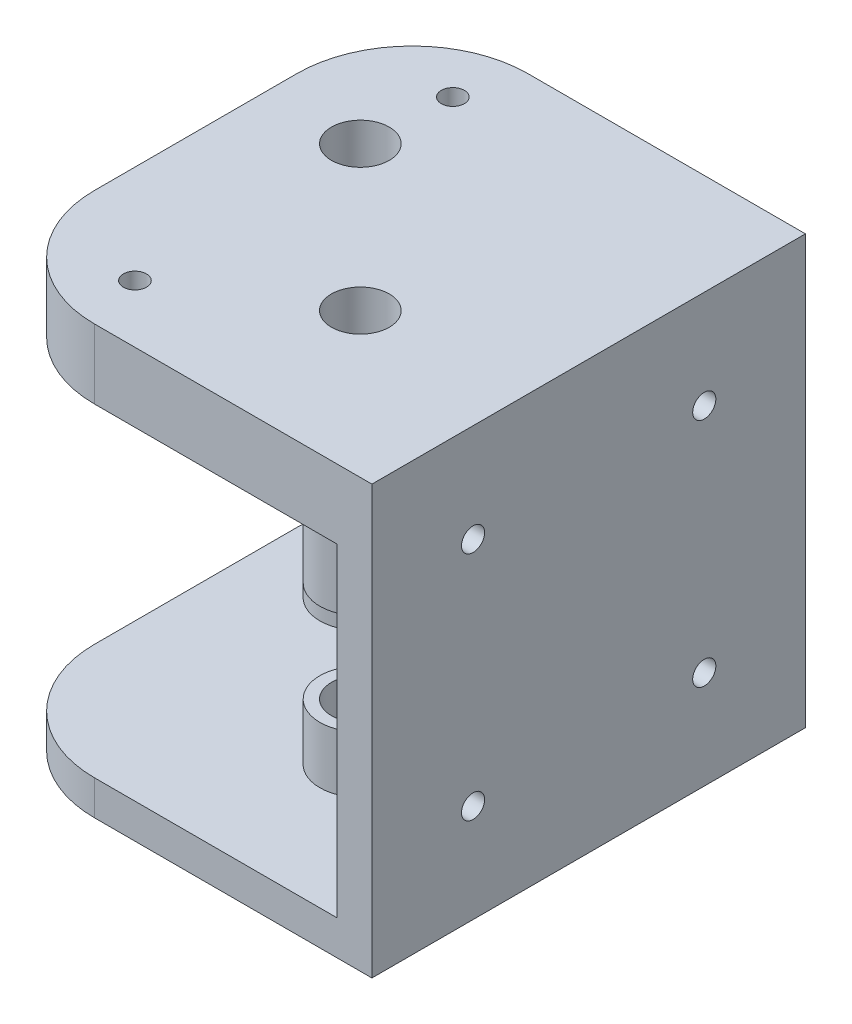
SolidWorks part; units mm, degrees
ref_plane "Front Plane" through (0, 0, 0) normal (0, 0, 1) x (1, 0, 0)
ref_plane "Top Plane" through (0, 0, 0) normal (0, 1, 0) x (1, 0, 0)
ref_plane "Right Plane" through (0, 0, 0) normal (1, 0, 0) x (0, 0, -1)
sketch "TopSketch1" plane through (0, 0, 0) normal (0, 1, 0) x (1, 0, 0)
  line L1 (0, 0) -> (34, 0)
  line L2 (0, 0) -> (0, 37.5)
  line L3 (0, 37.5) -> (34, 37.5)
  line L4 (34, 0) -> (34, 37.5)
  circle A0 centre (8.5, 32.5) radius 1
  circle A1 centre (8.5, 5) radius 1
  circle A2 centre (20.5, 12.5) radius 2.5
  circle A3 centre (8, 25) radius 2.5
  dimension "D7" = 2
  dimension "D8" = 5
  dimension "D2" = 12.5
  dimension "D3" = 12.5
  dimension "D4" = 5
  dimension "D5" = 5
  dimension "D10" = 37.5
  dimension "D9" = 12.5
  dimension "D12" = 13.5
  dimension "D6" = 25.5
  dimension "D11" = 8
  dimension "D13" = 12.5
extrude "Boss-Extrude1" add sketch "TopSketch1" along normal blind 6
sketch "TopLeftRiser" plane through (0, 0, 0) normal (0, -1, 0) x (1, 0, 0)
  line L0 (5.75, -27.681) -> (5.75, -37.5)
  line L1 (34, -37.5) -> (0, -37.5) construction
  line L2 (5.75, -37.5) -> (10.25, -37.5)
  line L3 (10.25, -37.5) -> (10.25, -27.681)
  arc A0 (10.25, -27.681) -> (5.75, -27.681) centre (8, -25) ccw
  circle A1 centre (8, -25) radius 2.5 construction
  circle A2 centre (8, -25) radius 2.5
  point P12 (8, -37.5)
  dimension "D1" = 7
  dimension "D2" = 4.5
extrude "TopLeftRiserBoss-Extrude2" add sketch "TopLeftRiser" along normal blind 4.9
sketch "TopRightRiser" plane through (0, 0, 0) normal (0, -1, 0) x (1, 0, 0)
  line L0 (18.25, -15.181) -> (18.25, -37.5)
  line L1 (34, -37.5) -> (10.25, -37.5) construction
  line L2 (18.25, -37.5) -> (22.75, -37.5)
  line L3 (22.75, -37.5) -> (22.75, -15.181)
  line L4 (5.75, -37.5) -> (10.25, -37.5) construction
  circle A0 centre (20.5, -12.5) radius 2.5
  circle A1 centre (20.5, -12.5) radius 2.5 construction
  arc A2 (22.75, -15.181) -> (18.25, -15.181) centre (20.5, -12.5) ccw
  arc A3 (10.25, -27.681) -> (5.75, -27.681) centre (8, -25) ccw construction
  point P15 (20.5, -37.5)
extrude "topRightRiserBoss-Extrude3" add sketch "TopRightRiser" along normal blind 14.4
sketch "MidWallSketch3" plane through (0, 0, 0) normal (0, -1, 0) x (1, 0, 0)
  line L1 (0, -34.5) -> (10.25, -34.5)
  line L2 (0, -34.5) -> (0, -37.5)
  line L3 (0, -37.5) -> (10.25, -37.5)
  line L4 (10.25, -34.5) -> (10.25, -37.5)
  line L5 (18.25, -34.5) -> (22.75, -34.5)
  line L6 (18.25, -34.5) -> (18.25, -37.5)
  line L7 (18.25, -37.5) -> (22.75, -37.5)
  line L8 (22.75, -34.5) -> (22.75, -37.5)
  line L9 (34, 0) -> (34, -37.5)
  line L10 (34, -37.5) -> (31, -37.5)
  line L11 (31, -37.5) -> (31, 0)
  line L14 (10.25, -37.5) -> (10.25, -27.681) construction
  line L15 (0, -37.5) -> (0, 0) construction
  line L16 (34, -37.5) -> (0, -37.5) construction
  line L17 (31, 0) -> (34, 0)
  line L19 (34, 0) -> (34, -37.5) construction
  line L20 (0, 0) -> (34, 0) construction
  line L21 (22.75, -37.5) -> (22.75, -15.181) construction
  line L22 (18.25, -15.181) -> (18.25, -37.5) construction
  dimension "D1" = 3
extrude "WallBoss-Extrude4" add sketch "MidWallSketch3" along normal blind 28
sketch "BottomSketch4" plane through (0, -28, 0) normal (0, -1, 0) x (1, 0, 0)
  line L0 (0, 0) -> (34, 0) construction
  line L1 (0, 0) -> (34, 0)
  line L2 (0, 0) -> (0, -37.5)
  line L3 (0, -37.5) -> (34, -37.5)
  line L4 (34, 0) -> (34, -37.5)
  line L5 (34, 0) -> (34, -37.5) construction
  line L6 (34, -37.5) -> (0, -37.5) construction
extrude "BottomBoss-Extrude5" add sketch "BottomSketch4" along normal blind 3
sketch "LowerLeftRiser" plane through (0, -28, 0) normal (0, 1, 0) x (1, 0, 0)
  line L0 (5.75, 27.681) -> (5.75, 34.5)
  line L1 (5.75, 34.5) -> (10.25, 34.5)
  line L2 (10.25, 34.5) -> (10.25, 27.681)
  line L3 (5.75, 34.5) -> (10.25, 34.5) construction
  line L4 (5.75, 27.681) -> (5.75, 34.5) construction
  line L5 (10.25, 34.5) -> (10.25, 27.681) construction
  circle A0 centre (8, 25) radius 2.5
  arc A1 (5.75, 27.681) -> (10.25, 27.681) centre (8, 25) ccw
  circle A2 centre (8, 25) radius 2.5 construction
  arc A3 (5.75, 27.681) -> (10.25, 27.681) centre (8, 25) ccw construction
extrude "LowerLeftRiserBoss-Extrude6" add sketch "LowerLeftRiser" along normal blind 14.4
sketch "LowerRightRiser" plane through (0, -28, 0) normal (0, 1, 0) x (1, 0, 0)
  line L0 (18.25, 15.181) -> (18.25, 34.5)
  line L1 (18.25, 34.5) -> (22.75, 34.5)
  line L2 (22.75, 34.5) -> (22.75, 15.181)
  line L3 (18.25, 34.5) -> (22.75, 34.5) construction
  line L4 (18.25, 15.181) -> (18.25, 34.5) construction
  line L5 (22.75, 34.5) -> (22.75, 15.181) construction
  circle A0 centre (20.5, 12.5) radius 2.5
  circle A1 centre (20.5, 12.5) radius 2.5 construction
  arc A2 (18.25, 15.181) -> (22.75, 15.181) centre (20.5, 12.5) ccw
  arc A3 (18.25, 15.181) -> (22.75, 15.181) centre (20.5, 12.5) ccw construction
extrude "LowerRightRiserBoss-Extrude7" add sketch "LowerRightRiser" along normal blind 4.9
fillet "Fillet1" radius 10 3 edges at (0, -29.5, 0) (0, 3, 0) (0, -12.5, -37.5)
sketch "GBMountingHolesSketch7" plane through (34, 0, 0) normal (1, 0, 0) x (0, 0, -1)
  line L0 (37.5, 6) -> (37.5, -31) construction
  line L1 (0, 6) -> (37.5, 6) construction
  line L2 (37.5, -31) -> (0, -31) construction
  line L3 (0, 6) -> (0, -31) construction
  circle A0 centre (8.75, -2.5) radius 1
  circle A1 centre (8.75, -22.5) radius 1
  circle A2 centre (28.75, -22.5) radius 1
  circle A3 centre (28.75, -2.5) radius 1
  dimension "D7" = 2
  dimension "D1" = 20
  dimension "D2" = 8.75
  dimension "D3" = 8.5
  dimension "D4" = 20
  dimension "D5" = 8.5
  dimension "D6" = 8.75
sketch "TopLeftInset" plane through (0, -4.9, 0) normal (0, -1, 0) x (1, 0, 0)
  line L0 (5.75, -27.681) -> (5.75, -34.5)
  line L1 (5.75, -34.5) -> (10.25, -34.5)
  line L2 (10.25, -34.5) -> (10.25, -27.681)
  line L3 (10.25, -34.5) -> (5.75, -34.5) construction
  line L4 (5.75, -34.5) -> (5.75, -27.681) construction
  line L5 (10.25, -27.681) -> (10.25, -34.5) construction
  arc A0 (5.75, -27.681) -> (10.25, -27.681) centre (8, -25) ccw
  arc A1 (10.25, -27.681) -> (5.75, -27.681) centre (8, -25) ccw construction
extrude "TopLeftInsetCut-Extrude1" cut sketch "TopLeftInset" against normal blind 1
sketch "TopRightInset" plane through (0, -14.4, 0) normal (0, -1, 0) x (1, 0, 0)
  line L0 (18.25, -15.181) -> (18.25, -34.5)
  line L1 (18.25, -34.5) -> (22.75, -34.5)
  line L2 (22.75, -34.5) -> (22.75, -15.181)
  line L3 (22.75, -34.5) -> (18.25, -34.5) construction
  line L4 (18.25, -34.5) -> (18.25, -15.181) construction
  line L5 (22.75, -15.181) -> (22.75, -34.5) construction
  arc A0 (18.25, -15.181) -> (22.75, -15.181) centre (20.5, -12.5) ccw
  arc A1 (22.75, -15.181) -> (18.25, -15.181) centre (20.5, -12.5) ccw construction
extrude "TopRightInsetCut-Extrude2" cut sketch "TopRightInset" against normal blind 1
sketch "LowerLeftInset" plane through (0, -13.6, 0) normal (0, 1, 0) x (1, 0, 0)
  line L0 (5.75, 27.681) -> (5.75, 34.5)
  line L1 (5.75, 34.5) -> (10.25, 34.5)
  line L2 (10.25, 34.5) -> (10.25, 27.681)
  line L3 (5.75, 34.5) -> (10.25, 34.5) construction
  line L4 (5.75, 27.681) -> (5.75, 34.5) construction
  line L5 (10.25, 34.5) -> (10.25, 27.681) construction
  arc A0 (10.25, 27.681) -> (5.75, 27.681) centre (8, 25) ccw
  arc A1 (5.75, 27.681) -> (10.25, 27.681) centre (8, 25) ccw construction
extrude "LowerLeftInsetCut-Extrude3" cut sketch "LowerLeftInset" against normal blind 1
sketch "LowerRightInset" plane through (0, -23.1, 0) normal (0, 1, 0) x (1, 0, 0)
  line L0 (18.25, 15.181) -> (18.25, 34.5)
  line L1 (18.25, 34.5) -> (22.75, 34.5)
  line L2 (22.75, 34.5) -> (22.75, 15.181)
  line L3 (18.25, 34.5) -> (22.75, 34.5) construction
  line L4 (18.25, 15.181) -> (18.25, 34.5) construction
  line L5 (22.75, 34.5) -> (22.75, 15.181) construction
  arc A2 (22.75, 15.181) -> (18.25, 15.181) centre (20.5, 12.5) ccw
  arc A3 (18.25, 15.181) -> (22.75, 15.181) centre (20.5, 12.5) ccw construction
extrude "LowerRightInsetCut-Extrude4" cut sketch "LowerRightInset" against normal blind 1
extrude "GBMountingHolesCut-Extrude5" cut sketch "GBMountingHolesSketch7" against normal blind 3
sketch "PushPinHoleSketch1" plane through (0, -31, 0) normal (0, -1, 0) x (1, 0, 0)
  circle A0 centre (20.5, -12.5) radius 1
  circle A1 centre (8, -25) radius 1
  circle A2 centre (8, -25) radius 2.5 construction
  circle A3 centre (20.5, -12.5) radius 2.5 construction
  dimension "D1" = 2
extrude "Cut-Extrude1" cut sketch "PushPinHoleSketch1" against normal through all
equation "\"GABDepth\"= \"GABDistanceFromBackToFirstPulley\" + \"GABPulleyDDistanceBetween\" + \"GABDistanceFromPulleyToFront\""
equation "\"GABWidth\"= \"StandardWallThickness\" + \"GABDistanceFromLSideToPulley\" + \"GABPulleyWDistanceBetween\" + \"GABDistanceFromPulleyToRSide\""
equation "\"GABLowerHeight\"= 3mm"
equation "\"GABUpperHeight\"= 6mm"
equation "\"GABMidWallHeight\"= 28mm'Must equal 28 or changes alignment"
equation "\"StandardWallThickness\"= 3mm"
equation "\"GABMidShortRiserHeight\"= \"GABMidWallHeight\" / 2 - \"20TGT2PulleyWidth\"'Equals 5.3"
equation "\"LinearGBMountHolesXDistance\"= 20mm'Spec"
equation "\"GABHeight\"= \"GABLowerHeight\" + \"GABMidWallHeight\" + \"GABUpperHeight\""
equation "\"GBMountingHoleDiameter\"= 2mm"
equation "\"GABMidLongRiserHeight\"= \"GABMidWallHeight\" - \"GABMidShortRiserHeight\" - \"20TGT2PulleyWidth\"'Equals 14"
equation "\"GABLRClampHoleOffsetFromSide\"= 5mm"
equation "\"GABDistanceFromBackToFirstPulley\"= 13.5mm"
equation "\"GABPulleyDDistanceBetween\"= 12.5mm'From the100"
equation "\"GABPulleyWDistanceBetween\"= 14.5mm'From the100"
equation "\"GABDistanceFromPulleyToFront\"= 8mm"
equation "\"GABDistanceFromLSideToPulley\"= 9.5mm + \"StandardWallThickness\""
equation "\"GABDistanceFromPulleyToRSide\"= 7.5mm"
equation "\"GABDistanceToFrontClampHoles\"= 8.5mm"
equation "\"SteelShaft5mmHoleDiameter\"= 5mm"
equation "\"20TGT2PulleyWidth\"= 8.7mm'The STL of the Pulley in the diagram is a bit larger"
equation "\"7mmx1mmSpacerDiameter\"= 7mm"
equation "\"7mmx1mmSpacerHeight\"= 1mm"
equation "\"GABRiserBossOffset\"= 0.8mm'Aligns Pulleys"
equation "\"D2@TopSketch1\" = \"GABPulleyDDistanceBetween\""
equation "\"D3@TopSketch1\" = \"GABPulleyDDistanceBetween\""
equation "\"D4@TopSketch1\" = \"GABLRClampHoleOffsetFromSide\""
equation "\"D5@TopSketch1\" = \"GABLRClampHoleOffsetFromSide\""
equation "\"D8@TopSketch1\" = \"SteelShaft5mmHoleDiameter\""
equation "\"D10@TopSketch1\" = \"GABWidth\""
equation "\"D9@TopSketch1\" = \"GABDistanceFromLSideToPulley\""
equation "\"D12@TopSketch1\"=\"GABDistanceFromBackToFirstPulley\""
equation "\"D1@Boss-Extrude1\"=\"GABUpperHeight\""
equation "\"D1@TopLeftRiser\" = \"7mmx1mmSpacerDiameter\""
equation "\"D1@TopLeftRiserBoss-Extrude2\"=\"GABMidShortRiserHeight\" - \"GABRiserBossOffset\" / 2"
equation "\"D1@topRightRiserBoss-Extrude3\"=\"GABMidLongRiserHeight\" + \"GABRiserBossOffset\"/2"
equation "\"D1@WallBoss-Extrude4\" = \"GABMidWallHeight\""
equation "\"D1@BottomBoss-Extrude5\" = \"GABLowerHeight\""
equation "\"D1@LowerLeftRiserBoss-Extrude6\"=\"GABMidLongRiserHeight\" + \"GABRiserBossOffset\"/2"
equation "\"D1@LowerRightRiserBoss-Extrude7\"=\"GABMidShortRiserHeight\"-\"GABRiserBossOffset\"/2"
equation "\"D1@GBMountingHolesSketch7\" = \"LinearGBMountHolesXDistance\""
equation "\"D2@GBMountingHolesSketch7\" =  ( \"GABWidth\" - \"LinearGBMountHolesXDistance\" )  / 2"
equation "\"D3@GBMountingHolesSketch7\" =  ( \"GABHeight\" - \"LinearGBMountHolesXDistance\" )  / 2"
equation "\"D4@GBMountingHolesSketch7\"=\"LinearGBMountHolesYDistance\""
equation "\"D7@GBMountingHolesSketch7\"=\"GBMountingHoleDiameter\""
equation "\"D1@TopLeftInsetCut-Extrude1\" = \"7mmx1mmSpacerHeight\""
equation "\"D1@TopRightInsetCut-Extrude2\" = \"7mmx1mmSpacerHeight\""
equation "\"D1@LowerLeftInsetCut-Extrude3\" = \"7mmx1mmSpacerHeight\""
equation "\"D1@LowerRightInsetCut-Extrude4\" = \"7mmx1mmSpacerHeight\""
equation "\"D1@GBMountingHolesCut-Extrude5\" = \"StandardWallThickness\""
equation "\"D6@TopSketch1\"=\"GABDepth\" - \"GABDistanceToFrontClampHoles\""
equation "\"D11@TopSketch1\"=\"GABDistanceFromPulleyToFront\""
equation "\"LinearGBMountHolesYDistance\"= 20mm'Spec"
equation "\"StealPinPushHoleDiameter\"= 2mm"
equation "\"D1@PushPinHoleSketch1\" = \"StealPinPushHoleDiameter\""
